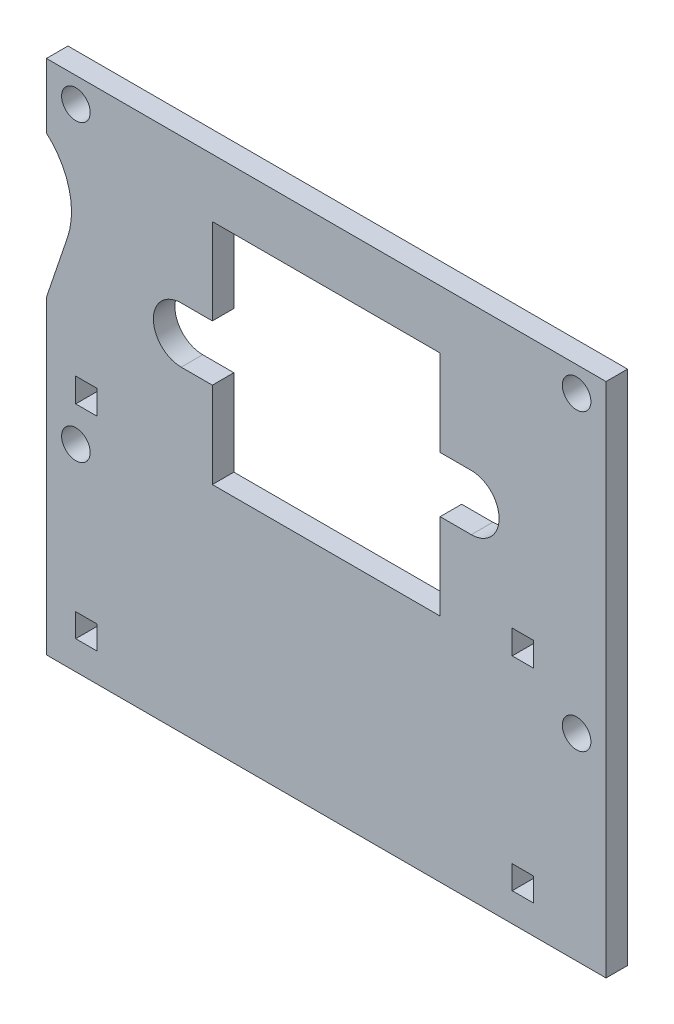
SolidWorks part; units mm, degrees
material "Beech"
ref_plane "Front Plane" through (0, 0, 0) normal (0, 0, 1) x (1, 0, 0)
ref_plane "Top Plane" through (0, 0, 0) normal (0, 1, 0) x (1, 0, 0)
ref_plane "Right Plane" through (0, 0, 0) normal (1, 0, 0) x (0, 0, -1)
sketch "Sketch1" plane through (0, 0, 0) normal (0, 0, 1) x (1, 0, 0)
  line L0 (-20.6375, 0) -> (20.6375, 0)
  line L1 (-20.6375, 22.8481) -> (-19.0799, 27.45)
  line L2 (13.716, 3.8411) -> (13.716, 2.1139)
  line L3 (-18.4785, 3.8411) -> (-16.891, 3.8411)
  line L4 (-18.4785, 3.8411) -> (-18.4785, 2.1139)
  line L5 (-18.4785, 2.1139) -> (-16.891, 2.1139)
  line L6 (-16.891, 3.8411) -> (-16.891, 2.1139)
  line L7 (15.3035, 2.1139) -> (13.716, 2.1139)
  line L8 (15.3035, 3.8411) -> (15.3035, 2.1139)
  line L9 (15.3035, 3.8411) -> (13.716, 3.8411)
  line L22 (-16.891, 17.1139) -> (-16.891, 18.8919)
  line L23 (-18.4785, 17.1139) -> (-16.891, 17.1139)
  line L24 (-18.4785, 18.8919) -> (-18.4785, 17.1139)
  line L25 (-16.891, 18.8919) -> (-18.4785, 18.8919)
  line L26 (-16.891, 17.1139) -> (-16.891, 18.8919)
  line L27 (-18.4785, 17.1139) -> (-16.891, 17.1139)
  line L28 (-18.4785, 18.8919) -> (-18.4785, 17.1139)
  line L29 (-16.891, 18.8919) -> (-18.4785, 18.8919)
  line L44 (0, 14.605) -> (0, 24.13) construction
  line L45 (-8.4, 23.35) -> (-8.4, 17)
  line L46 (-20.6375, 0) -> (-20.6375, 38.1)
  line L47 (-20.6375, 38.1) -> (20.6375, 38.1)
  line L48 (20.6375, 0) -> (20.6375, 38.1)
  line L49 (-20.6375, 25.4) -> (20.6375, 25.4) construction
  line L50 (8.4, 33.8) -> (-8.4, 33.8)
  line L53 (-18.4785, 2.1139) -> (-18.4785, 3.8919) construction
  line L58 (15.3035, 17.1139) -> (15.3035, 18.8919)
  line L59 (13.716, 17.1139) -> (15.3035, 17.1139)
  line L60 (8.4, 33.8) -> (8.4, 27.45)
  line L61 (8.4, 17) -> (-8.4, 17)
  line L62 (-8.4, 33.8) -> (-8.4, 27.45)
  line L63 (8.4, 33.8) -> (-8.4, 17) construction
  line L64 (8.4, 17) -> (-8.4, 33.8) construction
  line L65 (13.716, 18.8919) -> (13.716, 17.1139)
  line L66 (-8.4, 23.35) -> (-10.7, 23.35)
  line L67 (8.4, 23.35) -> (10.7, 23.35)
  line L68 (-8.4, 27.45) -> (-10.7, 27.45)
  line L69 (8.4, 27.45) -> (10.7, 27.45)
  line L70 (15.3035, 18.8919) -> (13.716, 18.8919)
  line L71 (8.4, 23.35) -> (8.4, 17)
  line L72 (15.3035, 17.1139) -> (15.3035, 18.8919)
  line L73 (13.716, 17.1139) -> (15.3035, 17.1139)
  line L74 (13.716, 18.8919) -> (13.716, 17.1139)
  line L75 (15.3035, 18.8919) -> (13.716, 18.8919)
  arc A0 (-10.7, 23.35) -> (-10.7, 27.45) centre (-10.7, 25.4) cw
  arc A1 (10.7, 23.35) -> (10.7, 27.45) centre (10.7, 25.4) ccw
  circle A2 centre (-18.4658, 36.2585) radius 1.0541
  circle A3 centre (-18.4658, 14.5415) radius 1.0541
  circle A4 centre (18.4658, 14.5415) radius 1.0541
  circle A5 centre (18.4658, 36.2585) radius 1.0541
  arc A6 (-20.6375, 33.337) -> (-19.0799, 27.45) centre (-24.3025, 29.2177) cw
  point P0 (0, 0)
  point P56 (0, 25.4)
  point P60 (0, 38.1)
  dimension "D14" = 12.7
  dimension "D4" = 2.1082
  dimension "D3" = 38.1
  dimension "D9" = 0
  dimension "D11" = 0
  dimension "D12" = 41.275
  dimension "D13" = 13.716
  dimension "D15" = 16.8
  dimension "D16" = 2.1139
  dimension "D17" = 2.1139
  dimension "D19" = 16.8
  dimension "D20" = 4.1
  dimension "D21" = 2.3
  dimension "D5" = 2.1717
  dimension "D6" = 1.8415
  dimension "D7" = 1.7272
  dimension "D8" = 1.5875
extrude "Boss-Extrude1" add sketch "Sketch1" along normal blind 1.5875 contours L48 L47 L46 L69 region at (-20.0758, 11.424, 0)
fillet "Fillet7" [suppressed] radius 15.24
